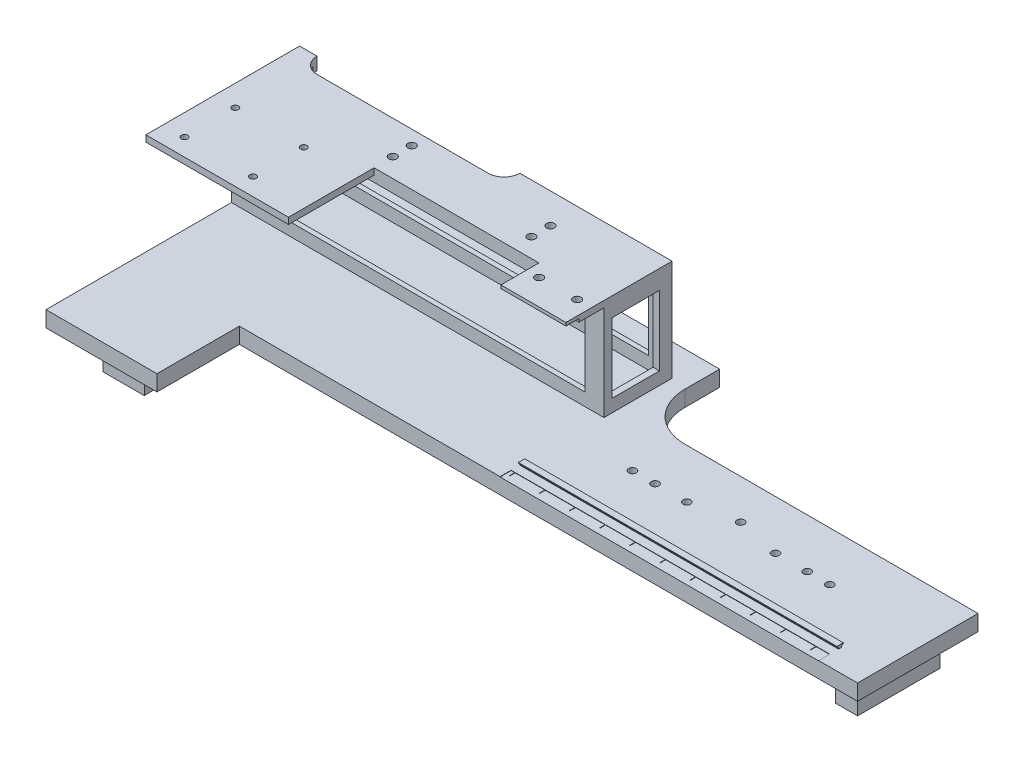
SolidWorks part; units mm, degrees
ref_plane "前视基准面" through (0, 0, 0) normal (0, 0, 1) x (1, 0, 0)
ref_plane "上视基准面" through (0, 0, 0) normal (0, 1, 0) x (1, 0, 0)
ref_plane "右视基准面" through (0, 0, 0) normal (1, 0, 0) x (0, 0, -1)
other "Configuration Table"
sketch "草图1" plane through (0, 0, 0) normal (0, 1, 0) x (1, 0, 0)
  line L1 (-1150, 300) -> (1150, 300)
  line L2 (-1150, 300) -> (-1150, -300)
  line L3 (-1150, -300) -> (1150, -300)
  line L4 (1150, 300) -> (1150, -300)
  line L5 (-1150, 300) -> (1150, -300) construction
  line L6 (-1150, -300) -> (1150, 300) construction
  point P0 (0, 0)
  dimension "D1" = 600
  dimension "D2" = 2300
extrude "凸台-拉伸1" add sketch "草图1" along normal blind 50
sketch "草图3" plane through (0, 0, 0) normal (0, -1, 0) x (1, 0, 0)
  line L1 (-1150, 300) -> (-800, 300)
  line L2 (-1150, 300) -> (-1150, 320)
  line L3 (-1150, 320) -> (-800, 320)
  line L4 (-800, 300) -> (-800, 320)
  dimension "D1" = 20
  dimension "D2" = 350
extrude "凸台-拉伸3" add sketch "草图3" against normal blind 50
sketch "草图5" plane through (0, 50, 0) normal (0, 1, 0) x (1, 0, 0)
  line L0 (-1150, 300) -> (-1150, -320) construction
  line L1 (-1150, -320) -> (-800, -320)
  line L2 (-1150, -320) -> (-1150, -800)
  line L3 (-1150, -800) -> (-800, -800)
  line L4 (-800, -320) -> (-800, -800)
  line L5 (-800, -300) -> (1150, -300) construction
  dimension "D1" = 350
  dimension "D2" = 500
extrude "凸台-拉伸4" add sketch "草图5" against normal blind 50
sketch "草图6" plane through (0, 50, 0) normal (0, 1, 0) x (1, 0, 0)
  line L0 (-1150, 300) -> (-1150, -800) construction
  line L1 (-1150, -580) -> (-800, -580)
  line L2 (-1150, -580) -> (-1150, -600)
  line L3 (-1150, -600) -> (-800, -600)
  line L4 (-800, -580) -> (-800, -600)
  line L5 (-800, -300) -> (-800, -800) construction
  line L6 (-800, -300) -> (1150, -300) construction
  line L7 (-1150, -800) -> (-800, -800) construction
  dimension "D1" = 280
  dimension "D2" = 200
extrude "凸台-拉伸5" add sketch "草图6" along normal blind 300
sketch "草图7" plane through (0, 0, 600) normal (0, 0, 1) x (1, 0, 0)
  line L0 (-1150, 350) -> (-800, 350) construction
  line L1 (-1150, 350) -> (-1150, 50) construction
  circle A0 centre (-1130, 330) radius 10
  circle A1 centre (-1095, 330) radius 10
  circle A2 centre (-1060, 330) radius 10
  circle A3 centre (-1025, 330) radius 10
  circle A4 centre (-990, 330) radius 10
  circle A5 centre (-955, 330) radius 10
  circle A6 centre (-920, 330) radius 10
  circle A7 centre (-885, 330) radius 10
  circle A8 centre (-850, 330) radius 10
  circle A9 centre (-815, 330) radius 10
  dimension "D1" = 20
  dimension "D2" = 20
  dimension "D3" = 20
  dimension "D4" = 10
extrude "切除-拉伸2" cut sketch "草图7" against normal blind 300
sketch "草图8" plane through (0, 0, 600) normal (0, 0, 1) x (1, 0, 0)
  line L1 (-1150, 350) -> (-1150, 50) construction
  circle A0 centre (-1112.5, 300) radius 10
  circle A1 centre (-1095, 330) radius 10 construction
  circle A2 centre (-1077.5, 300) radius 10
  circle A3 centre (-1042.5, 300) radius 10
  circle A4 centre (-1007.5, 300) radius 10
  circle A5 centre (-972.5, 300) radius 10
  circle A6 centre (-937.5, 300) radius 10
  circle A7 centre (-902.5, 300) radius 10
  circle A8 centre (-867.5, 300) radius 10
  circle A9 centre (-832.5, 300) radius 10
  dimension "D1" = 30
  dimension "D2" = 20
  dimension "D3" = 37.5
  dimension "D4" = 9
extrude "切除-拉伸3" cut sketch "草图8" against normal blind 50
pattern_linear "阵列(线性)1" count 4 spacing 60 along (0, -1, 0) of "切除-拉伸2", "切除-拉伸3"
chamfer "倒角1" distance 20 angle 45 1 edges at (-975, 50, 580)
chamfer "倒角2" distance 20 angle 45 1 edges at (-975, 50, 600)
sketch "草图11" plane through (0, 50, 0) normal (0, 1, 0) x (1, 0, 0)
  line L1 (-1020, -637.5367) -> (-930, -637.5367)
  line L2 (-1020, -637.5367) -> (-1020, -677.5367)
  line L3 (-1020, -677.5367) -> (-930, -677.5367)
  line L4 (-930, -637.5367) -> (-930, -677.5367)
extrude "切除-拉伸5" cut sketch "草图11" against normal blind 2
sketch "草图13" plane through (0, 50, 0) normal (0, 1, 0) x (1, 0, 0)
  line L0 (1135, -300) -> (1150, -300)
  line L1 (-800, -300) -> (-785, -300)
  line L2 (-800, -300) -> (-800, 300)
  line L3 (-800, 300) -> (1150, 300)
  line L4 (1150, -300) -> (1150, 300)
  line L6 (-785, -300) -> (-785, 285)
  line L7 (-785, 285) -> (1135, 285)
  line L8 (1135, -300) -> (1135, 285)
  dimension "D1" = 15
  dimension "D2" = 15
  dimension "D3" = 15
extrude "凸台-拉伸6" add sketch "草图13" along normal blind 400
sketch "草图14" plane through (-800, 0, 0) normal (-1, 0, 0) x (0, 0, 1)
  line L0 (300, 450) -> (300, 50) construction
  line L1 (-300, 450) -> (300, 450)
  line L2 (-300, 450) -> (-300, 350)
  line L3 (-300, 350) -> (300, 350)
  line L4 (300, 450) -> (300, 350)
  line L5 (-300, 50) -> (560, 50) construction
  dimension "D1" = 300
extrude "切除-拉伸7" cut sketch "草图14" against normal blind 2368
sketch "草图15" plane through (0, 50, 0) normal (0, 1, 0) x (1, 0, 0)
  line L0 (-1150, 300) -> (-1150, -560) construction
  line L1 (-1150, 100) -> (1209.5756, 100)
  line L2 (-1150, 100) -> (-1150, -299.8306)
  line L3 (-1150, -299.8306) -> (1209.5756, -299.8306)
  line L4 (1209.5756, 100) -> (1209.5756, -299.8306)
  dimension "D1" = 100
extrude "切除-拉伸8" cut sketch "草图15" along normal blind 2368
sketch "草图16" plane through (0, 50, 0) normal (0, 1, 0) x (1, 0, 0)
  line L0 (1150, -299.8306) -> (1150, 100) construction
  line L1 (-800, 100) -> (1150, 100)
  line L2 (-800, 100) -> (-800, 85)
  line L3 (-800, 85) -> (1150, 85)
  line L4 (1150, 100) -> (1150, 85)
  dimension "D1" = 15
extrude "凸台-拉伸7" add sketch "草图16" along normal up to surface (300 mm away) up to face at (175, 350, -196.25)
sketch "草图17" plane through (0, 350, 0) normal (0, 1, 0) x (1, 0, 0)
  line L1 (-1150, 300) -> (-800, 300)
  line L2 (-1150, 300) -> (-1150, -299.8306)
  line L3 (-1150, -299.8306) -> (-800, -299.8306)
  line L4 (-800, 85) -> (-800, -299.8306)
  line L5 (-800, 300) -> (1150, 300)
  line L7 (-800, 85) -> (1150, 85)
  line L8 (1150, 300) -> (1150, 85)
sketch "草图18" plane through (0, 50, 0) normal (0, 1, 0) x (1, 0, 0)
  circle A0 centre (-800, -300) radius 17.9938
extrude "切除-拉伸9" cut sketch "草图18" along normal blind 2368
extrude "凸台-拉伸11" add sketch "草图17" along normal blind 20
sketch "草图20" plane through (0, 50, 0) normal (0, 1, 0) x (1, 0, 0)
  circle A0 centre (1150, -300) radius 52.3169
extrude "切除-拉伸10" cut sketch "草图20" along normal blind 556
sketch "草图21" plane through (0, 0, -85) normal (0, 0, 1) x (1, 0, 0)
  line L0 (1110, 90) -> (1110, 330)
  line L1 (1110, 330) -> (-760, 330)
  line L2 (-760, 330) -> (-760, 330)
  line L3 (-760, 330) -> (-760, 90)
  line L4 (-760, 90) -> (1110, 90)
  line L5 (1150, 50) -> (1150, 370)
  line L6 (1150, 370) -> (-800, 370)
  line L7 (-800, 370) -> (-800, 350)
  line L8 (-800, 350) -> (-800, 50)
  line L9 (-800, 50) -> (1150, 50)
  line L10 (1150, 50) -> (1150, 370) construction
  line L11 (1150, 370) -> (-800, 370) construction
  line L12 (-800, 370) -> (-800, 350) construction
  line L13 (-800, 350) -> (-800, 50) construction
  line L14 (-800, 50) -> (1150, 50) construction
  dimension "D1" = 0
  dimension "D2" = 40
extrude "切除-拉伸11" cut sketch "草图21" against normal blind 556
sketch "草图22" plane through (-800, 0, 0) normal (-1, 0, 0) x (0, 0, 1)
  line L0 (-260, 90) -> (-125, 90)
  line L1 (-125, 90) -> (-125, 310)
  line L2 (-125, 310) -> (-260, 310)
  line L3 (-260, 310) -> (-260, 90)
  line L4 (-300, 50) -> (-85, 50)
  line L5 (-85, 50) -> (-85, 350)
  line L6 (-85, 350) -> (-300, 350)
  line L7 (-300, 350) -> (-300, 50)
  line L8 (-300, 50) -> (-85, 50) construction
  line L9 (-85, 50) -> (-85, 350) construction
  line L10 (-85, 350) -> (-300, 350) construction
  line L11 (-300, 350) -> (-300, 50) construction
  dimension "D1" = 0
  dimension "D2" = 40
extrude "切除-拉伸13" cut sketch "草图22" against normal blind 1998
sketch "草图23" plane through (-800, 0, 0) normal (-1, 0, 0) x (0, 0, 1)
  line L1 (-300, 350) -> (-85, 350)
  line L2 (-300, 350) -> (-300, 50)
  line L3 (-300, 50) -> (-85, 50)
  line L4 (-85, 350) -> (-85, 50)
extrude "切除-拉伸14" cut sketch "草图23" against normal blind 50
sketch "草图24" plane through (-750, 0, 0) normal (-1, 0, 0) x (0, 0, 1)
  line L1 (-300, 350) -> (-285, 350)
  line L2 (-300, 350) -> (-300, 330)
  line L3 (-300, 330) -> (-285, 330)
  line L4 (-285, 350) -> (-285, 330)
  line L5 (-100, 350) -> (-85, 350)
  line L6 (-100, 350) -> (-100, 330)
  line L7 (-100, 330) -> (-85, 330)
  line L8 (-85, 350) -> (-85, 330)
  line L9 (-300, 90) -> (-285, 90)
  line L10 (-300, 90) -> (-300, 50)
  line L11 (-300, 50) -> (-285, 50)
  line L12 (-285, 90) -> (-285, 50)
  line L13 (-100, 90) -> (-85, 90)
  line L14 (-100, 90) -> (-100, 50)
  line L15 (-100, 50) -> (-85, 50)
  line L16 (-85, 90) -> (-85, 50)
extrude "凸台-拉伸13" add sketch "草图24" along normal up to surface (400 mm away) up to face at (-1150, 104, 454)
sketch "草图25" plane through (-1150, 0, 0) normal (-1, 0, 0) x (0, 0, 1)
  line L1 (-85, 370) -> (-300, 370)
  line L2 (-85, 370) -> (-85, 0)
  line L3 (-85, 0) -> (-300, 0)
  line L4 (-300, 370) -> (-300, 0)
  line L5 (-125, 310) -> (-260, 310)
  line L6 (-125, 310) -> (-125, 90)
  line L7 (-125, 90) -> (-260, 90)
  line L8 (-260, 310) -> (-260, 90)
extrude "凸台-拉伸14" add sketch "草图25" against normal blind 30
sketch "草图26" plane through (0, 0, -85) normal (0, 0, 1) x (1, 0, 0)
  line L0 (1110, 90) -> (25, 90)
  line L2 (1110, 330) -> (-1120, 330) construction
  line L3 (-800, 370) -> (1150, 370) construction
  line L5 (25, 330) -> (25, 90)
  line L7 (-35, 330) -> (-35, 90)
  line L9 (-35, 330) -> (-35, 370)
  line L11 (25, 330) -> (25, 370)
  line L12 (-800, 0) -> (1150, 0) construction
  line L14 (-35, 90) -> (-35, 0)
  line L16 (25, 90) -> (25, 0)
  line L17 (-35, 90) -> (-1120, 90)
  line L18 (-35, 0) -> (25, 0)
  line L19 (-35, 370) -> (25, 370)
  line L20 (-35, 370) -> (25, 370)
  line L21 (-35, 370) -> (-35, 0)
  line L22 (-35, 0) -> (25, 0)
  line L23 (25, 370) -> (25, 0)
  line M10 (-1120, 330) -> (1110, 330)
  line M12 (1110, 90) -> (-1120, 90)
  line M16 (-1150, 50) -> (1150, 50)
  line M18 (1150, 370) -> (-800, 370)
extrude "凸台-拉伸16" add sketch "草图26" against normal up to surface (215 mm away) contours L7 L5 M10 M12 | L11 L9 M10 M18 | L16 L14 M12 M16 | L21 L20 L23 L22 region at (-5, 350, -85) region at (-5, 210, -85) region at (-5, 70, -85) up to face at (-5, 210, -300)
sketch "草图28" plane through (-35, 0, 0) normal (-1, 0, 0) x (0, 0, 1)
  line L1 (-285, 350) -> (-100, 350)
  line L2 (-285, 350) -> (-285, 50)
  line L3 (-285, 50) -> (-100, 50)
  line L4 (-100, 350) -> (-100, 50)
extrude "切除-拉伸16" cut sketch "草图28" against normal blind 89
sketch "草图29" plane through (0, 0, 0) normal (0, -1, 0) x (-1, 0, 0)
  line L1 (1150, 300) -> (-1150, 300)
  line L2 (1150, 300) -> (1150, 400)
  line L3 (1150, 400) -> (-1150, 400)
  line L4 (-1150, 300) -> (-1150, 400)
  dimension "D1" = 100
extrude "凸台-拉伸17" add sketch "草图29" against normal blind 50
sketch "草图30" plane through (0, 370, 0) normal (0, 1, 0) x (1, 0, 0)
  circle A0 centre (-1082.9308, 30) radius 10
  circle A1 centre (-1082.9308, -130) radius 10
  circle A2 centre (-867.0692, 30) radius 10
  circle A3 centre (-867.0692, -130) radius 10
extrude "切除-拉伸17" cut sketch "草图30" against normal blind 50
sketch "草图31" plane through (-800, 0, 0) normal (1, 0, 0) x (0, 0, -1)
  line L0 (-170, 370) -> (-170, 390) construction
  line L1 (-321.6973, 391.2845) -> (-185, 391.2845)
  line L2 (-321.6973, 391.2845) -> (-321.6973, 329.5415)
  line L3 (-321.6973, 329.5415) -> (-185, 329.5415)
  line L4 (-185, 391.2845) -> (-185, 329.5415)
  dimension "D1" = 15
extrude "切除-拉伸18" cut sketch "草图31" against normal through all both and the other way through all
sketch "草图32" plane through (0, 50, 0) normal (0, 1, 0) x (1, 0, 0)
  line L0 (1150, 85) -> (1150, -300) construction
  line L2 (1150, -107.5) -> (-729.851, -107.5) construction
  line L3 (-550, -107.5) -> (950, -107.5) construction
  line L4 (-550, -7.5) -> (950, -7.5)
  line L5 (-550, -207.5) -> (950, -207.5)
  arc A0 (-550, -7.5) -> (-550, -207.5) centre (-550, -107.5) ccw
  arc A1 (950, -207.5) -> (950, -7.5) centre (950, -107.5) ccw
  point P8 (200, -107.5)
  dimension "D2" = 1500
  dimension "D1" = 100
  dimension "D3" = 200
sketch "草图33" plane through (0, 50, 0) normal (0, 1, 0) x (1, 0, 0)
  line L0 (-1150, 400) -> (-1150, 750)
  line L1 (-1150, 750) -> (-800, 750)
  line L2 (-800, 400) -> (-800, 750)
  line L3 (-1150, 400) -> (1150, 400) construction
  line L4 (-1150, 400) -> (-800, 400)
  dimension "D1" = 350
extrude "凸台-拉伸18" add sketch "草图33" against normal up to surface (50 mm away) up to face at (-266.6667, 0, 233.3333)
sketch "草图34" plane through (0, 50, 0) normal (0, 1, 0) x (1, 0, 0)
  line L1 (-800, -300) -> (-1418.7431, -300)
  line L3 (-800, -918.0987) -> (-1418.7431, -918.0987)
  line L4 (-1418.7431, -300) -> (-1418.7431, -918.0987)
  line L5 (-800, -300) -> (-665.2437, -300)
  line L7 (-800, -918.0987) -> (-665.2437, -918.0987)
  line L8 (-665.2437, -300) -> (-665.2437, -918.0987)
extrude "切除-拉伸20" cut sketch "草图34" against normal through all both and the other way through all
sketch "草图35" plane through (0, 50, 0) normal (0, 1, 0) x (1, 0, 0)
  line L1 (-1150, -300) -> (-800, -300)
  line L2 (-1150, -300) -> (-1150, -500)
  line L3 (-1150, -500) -> (-800, -500)
  line L4 (-800, -300) -> (-800, -500)
  dimension "D1" = 200
extrude "凸台-拉伸19" add sketch "草图35" against normal up to surface (50 mm away) up to face at (-266.6667, 0, -283.3333)
sketch "草图36" plane through (0, 50, 0) normal (0, 1, 0) x (1, 0, 0)
  line L6 (-1150, 85) -> (-1150, -500) construction
  line L7 (-1150, -205) -> (-800, -205)
  line L8 (-1150, -205) -> (-1150, -220)
  line L9 (-1150, -220) -> (-800, -220)
  line L10 (-800, -205) -> (-800, -220)
  line L11 (-800, -185) -> (-1150, -185) construction
  line L12 (-800, -500) -> (-800, -300) construction
  dimension "D1" = 20
  dimension "D2" = 15
  dimension "D3" = 0
extrude "凸台-拉伸20" add sketch "草图36" along normal blind 200
sketch "草图37" plane through (0, 0, 220) normal (0, 0, 1) x (1, 0, 0)
  line L0 (-1150, 250) -> (-800, 250) construction
  line L1 (-1150, 250) -> (-1150, 50) construction
  circle A0 centre (-1130, 230) radius 10
  circle A1 centre (-1095, 230) radius 10
  circle A2 centre (-1060, 230) radius 10
  circle A3 centre (-1025, 230) radius 10
  circle A4 centre (-990, 230) radius 10
  circle A5 centre (-955, 230) radius 10
  circle A6 centre (-920, 230) radius 10
  circle A7 centre (-885, 230) radius 10
  circle A8 centre (-850, 230) radius 10
  circle A9 centre (-815, 230) radius 10
  dimension "D1" = 20
  dimension "D2" = 20
  dimension "D3" = 20
  dimension "D4" = 10
extrude "切除-拉伸21" cut sketch "草图37" against normal blind 200 and the other way through all
sketch "草图38" plane through (0, 0, 220) normal (0, 0, 1) x (1, 0, 0)
  line L0 (-1130, 230) -> (-1095, 230) construction
  line L1 (-1095, 230) -> (-1095, 200) construction
  line L2 (-1095, 200) -> (-1130, 200) construction
  line L3 (-1130, 200) -> (-1130, 230) construction
  circle A0 centre (-1112.5, 200) radius 10
  circle A2 centre (-1077.5, 200) radius 10
  circle A3 centre (-1042.5, 200) radius 10
  circle A4 centre (-1007.5, 200) radius 10
  circle A5 centre (-972.5, 200) radius 10
  circle A6 centre (-937.5, 200) radius 10
  circle A7 centre (-902.5, 200) radius 10
  circle A8 centre (-867.5, 200) radius 10
  circle A9 centre (-832.5, 200) radius 10
  dimension "D2" = 20
  dimension "D3" = 9
  dimension "D1" = 30
extrude "切除-拉伸22" cut sketch "草图38" against normal blind 200
pattern_linear "阵列(线性)2" count 3 spacing 60 along (0, -1, 0) of "切除-拉伸22", "切除-拉伸21"
chamfer "倒角3" distance 10 angle 45 2 edges at (-975, 50, 205) (-975, 50, 220)
sketch "草图39" plane through (0, 50, 0) normal (0, 1, 0) x (1, 0, 0)
  line L0 (-800, -230) -> (-1150, -230) construction
  line L1 (-800, -500) -> (1294.0617, -500)
  line L2 (-800, -500) -> (-800, -240)
  line L3 (-800, -240) -> (1294.0617, -240)
  line L4 (1294.0617, -500) -> (1294.0617, -240)
  dimension "D1" = 10
extrude "切除-拉伸23" cut sketch "草图39" against normal blind 200
sketch "草图40" plane through (0, 370, 0) normal (0, 1, 0) x (1, 0, 0)
  line L1 (-800, 85) -> (-700, 85)
  line L2 (-800, 85) -> (-800, -185)
  line L3 (-800, -185) -> (-700, -185)
  line L4 (-700, 85) -> (-700, -185)
  dimension "D1" = 100
extrude "凸台-拉伸21" add sketch "草图40" against normal up to surface (20 mm away) up to face at (-1082.9308, 350, 140)
sketch "草图41" plane through (0, 50, 0) normal (0, 1, 0) x (1, 0, 0)
  line L0 (-800, 400) -> (-800, 750) construction
  line L1 (-1150, 750) -> (-800, 750)
  line L2 (-1150, 750) -> (-1150, 565)
  line L3 (-1150, 565) -> (-800, 565)
  line L4 (-800, 750) -> (-800, 565)
  dimension "D1" = 185
extrude "切除-拉伸24" cut sketch "草图41" against normal blind 200
sketch "草图42" plane through (0, 370, 0) normal (0, 1, 0) x (1, 0, 0)
  line L0 (-1045, 300) -> (-505.14, 300) construction
  line L1 (1150, 300) -> (-1150, 300) construction
  line L2 (-1045, 350) -> (-505.14, 350)
  line L3 (-1045, 250) -> (-505.14, 250)
  line L4 (-1035, 328) -> (-1035, 318.2276) construction
  line L5 (-515.14, 320) -> (-515.14, 328) construction
  arc A0 (-1045, 350) -> (-1045, 250) centre (-1045, 300) ccw
  arc A1 (-505.14, 250) -> (-505.14, 350) centre (-505.14, 300) ccw
  point P4 (-775.07, 300)
  dimension "D1" = 10
  dimension "D2" = 10
  dimension "D3" = 50
extrude "切除-拉伸25" cut sketch "草图42" against normal blind 200
sketch "草图43" plane through (0, 0, -300) normal (0, 0, -1) x (-1, 0, 0)
  line L0 (800, 50) -> (-1150, 50) construction
  line L1 (-1476.0177, 591.952) -> (-25, 591.952)
  line L2 (-1476.0177, 591.952) -> (-1476.0177, 50)
  line L3 (-1476.0177, 50) -> (-25, 50)
  line L4 (-25, 591.952) -> (-25, 50)
extrude "切除-拉伸26" cut sketch "草图43" against normal blind 532
sketch "草图44" plane through (25, 0, 0) normal (1, 0, 0) x (0, 0, -1)
  line L1 (85, 370) -> (300, 370)
  line L2 (85, 370) -> (85, 50)
  line L3 (85, 50) -> (300, 50)
  line L4 (300, 370) -> (300, 50)
  line L5 (125, 310) -> (260, 310)
  line L6 (125, 310) -> (125, 90)
  line L7 (125, 90) -> (260, 90)
  line L8 (260, 310) -> (260, 90)
extrude "凸台-拉伸22" add sketch "草图44" against normal blind 20
sketch "草图45" plane through (0, 50, 0) normal (0, 1, 0) x (1, 0, 0)
  circle A0 centre (-1090.5229, 522) radius 12
  circle A1 centre (-1090.5229, 444) radius 12
  circle A2 centre (-859.4771, 522) radius 12
  circle A3 centre (-859.4771, 444) radius 12
extrude "切除-拉伸27" cut sketch "草图45" against normal blind 80
sketch "草图46" plane through (0, 370, 0) normal (0, 1, 0) x (1, 0, 0)
  circle A0 centre (-701.1779, 205) radius 12.5
  circle A1 centre (-701.1779, 145) radius 12.5
  circle A2 centre (-263.624, 205) radius 12.5
  circle A3 centre (-263.624, 145) radius 12.5
extrude "切除-拉伸28" cut sketch "草图46" against normal blind 70
sketch "草图47" plane through (25, 0, 0) normal (1, 0, 0) x (0, 0, -1)
  line L0 (5.9634, 540) -> (5.9634, 390) construction
  line L1 (85, 370) -> (5.9634, 370)
  line L2 (85, 370) -> (85, 350)
  line L3 (85, 350) -> (5.9634, 350)
  line L4 (5.9634, 360) -> (5.9634, 350)
  line L5 (-185, 370) -> (85, 370) construction
  line L7 (5.9634, 350) -> (5.9634, 360)
  line L8 (5.9634, 370) -> (-35, 370)
  line L9 (-35, 360) -> (-35, 370)
  line L10 (-35, 370) -> (85, 370)
  line L13 (-35, 360) -> (5.9634, 360)
  line L14 (5.9634, 350) -> (5.9634, 360)
  line L15 (5.9634, 350) -> (85, 350)
  line L16 (85, 370) -> (-35, 370)
  line L17 (-35, 360) -> (5.9634, 360)
  line M12 (85, 370) -> (85, 50)
  dimension "D1" = 20
  dimension "D2" = 120
extrude "凸台-拉伸23" add sketch "草图47" against normal up to surface (205 mm away) contours L9 L13 L4 L3 L1 L8 M12 region at (25, 361.029, -33.1332)
sketch "草图48" plane through (0, 370, 0) normal (0, 1, 0) x (1, 0, 0)
  circle A0 centre (-140, 45.4817) radius 12.5
  circle A1 centre (-20, 45.4817) radius 12.5
extrude "切除-拉伸29" cut sketch "草图48" against normal blind 30
sketch "草图50" plane through (0, 50, 0) normal (0, 1, 0) x (1, 0, 0)
  line L0 (25, 300) -> (25, 463.9214)
sketch "草图51" plane through (0, 50, 0) normal (0, 1, 0) x (1, 0, 0)
  line L0 (1150, 140) -> (225, 140)
  line L1 (1150, 400) -> (1150, -240) construction
  line L2 (1150, -240) -> (-800, -240) construction
  line L5 (-800, 400) -> (1150, 400) construction
  line L6 (75, 400) -> (1150, 400)
  line L7 (1150, 400) -> (1150, 140)
  line L8 (75, 400) -> (75, 290)
  arc A0 (75, 290) -> (225, 140) centre (225, 290) ccw
  dimension "D2" = 150
  dimension "D1" = 380
  dimension "D3" = 1075
extrude "切除-拉伸31" cut sketch "草图51" against normal through all both and the other way through all
sketch "草图52" plane through (0, 50, 0) normal (0, 1, 0) x (1, 0, 0)
  line L0 (1150, -240) -> (-800, -240) construction
  line L1 (1030, -68.091) -> (1030, -28.091) construction
  line L2 (1030, -48.091) -> (1012.5, -48.091) construction
  line L4 (1027.5, 110) -> (1027.5, -90)
  line L7 (25, 300) -> (25, -35) construction
  line L8 (27.5, 110) -> (25, 110)
  line L9 (27.5, 110) -> (42.5, 110)
  line L10 (225, 140) -> (1150, 140) construction
  line L12 (42.5, -90) -> (1012.5, -90)
  line L14 (27.5, -105) -> (1027.5073, -105)
  line L15 (1027.5073, -105) -> (1027.5, -90)
  line L16 (1012.5, -90) -> (1012.5, 110)
  line L17 (42.5, -90) -> (42.5, 110)
  line L18 (1012.5, 110) -> (1027.5, 110)
  line L19 (42.5, -48.091) -> (25, -48.091) construction
  line L21 (27.5, -105) -> (25, -105)
  line L22 (25, 110) -> (25, -105)
  point P1 (527.5, -48.091)
  point P4 (527.5, -48.091)
  dimension "D1" = 150
  dimension "D2" = 30
  dimension "D3" = 15
  dimension "D4" = 15
extrude "凸台-拉伸24" add sketch "草图52" along normal blind 250 contours L14 L15 L4 L18 L16 L12 L17 L9 L8 L22 L21
sketch "草图53" plane through (25, 0, 0) normal (1, 0, 0) x (0, 0, -1)
  line L0 (150.071, 90) -> (110, 90)
  line L1 (125, 90) -> (260, 90) construction
  line L2 (110, 300) -> (110, 50) construction
  line L3 (110, 90) -> (110, 310)
  line L4 (110, 310) -> (177.1058, 310)
  line L5 (260, 310) -> (125, 310) construction
  line L6 (177.1058, 310) -> (150.071, 90)
extrude "切除-拉伸32" cut sketch "草图53" against normal mid plane 50
sketch "草图54" plane through (0, 0, -110) normal (0, 0, -1) x (-1, 0, 0)
  line L0 (-1012.5, 300) -> (-997.5, 260)
  line L1 (-997.5, 260) -> (-1012.5, 260)
  line L2 (-1012.5, 300) -> (-1012.5, 50) construction
  line L4 (-1012.5, 260) -> (-1012.5, 300)
extrude "凸台-拉伸25" add sketch "草图54" against normal up to surface (200 mm away) up to face at (527.5, 175, 90)
sketch "草图55" plane through (42.5, 0, 0) normal (1, 0, 0) x (0, 0, -1)
  line L0 (-90, 300) -> (-75, 260)
  line L1 (-75, 260) -> (-90, 260)
  line L2 (-90, 260) -> (-90, 300)
extrude "凸台-拉伸26" add sketch "草图55" along normal up to surface (985 mm away) up to face at (1027.5, 175, -10)
sketch "草图56" plane through (0, 0, -110) normal (0, 0, -1) x (-1, 0, 0)
  line L0 (-42.5, 300) -> (-57.5, 260)
  line L1 (-57.5, 260) -> (-42.5, 260)
  line L3 (-42.5, 300) -> (-42.5, 50) construction
  line L4 (-42.5, 260) -> (-42.5, 300)
extrude "凸台-拉伸27" add sketch "草图56" against normal up to surface (215 mm away) up to face at (526.2537, 175, 105)
sketch "草图57" plane through (25, 0, 0) normal (-1, 0, 0) x (0, 0, 1)
  line L0 (105, 180) -> (105, 170)
  line L1 (110, 180) -> (112.5, 185)
  line L2 (105, 180) -> (110, 180)
  line L4 (105, 170) -> (110, 170)
  line L8 (112.5, 185) -> (115, 185)
  line L9 (115, 185) -> (115, 165)
  line L10 (115, 165) -> (112.5, 165)
  line L11 (112.5, 165) -> (110, 170)
  point P4 (105, 175)
  dimension "D1" = 10
  dimension "D4" = 10
  dimension "D5" = 10
  dimension "D6" = 2.5
  dimension "D7" = 2.5
extrude "凸台-拉伸28" add sketch "草图57" against normal up to surface (1002.5 mm away) up to face at (1027.5, 175, -10)
sketch "草图58" plane through (0, 50, 0) normal (0, 1, 0) x (1, 0, 0)
  line L0 (1027.5073, -105) -> (1027.5073, -240) construction
  line L1 (1150, -240) -> (-800, -240) construction
  line L2 (1173.3497, -172.5) -> (-79.877, -172.5) construction
  line L4 (22.5073, -167.5) -> (1027.5073, -167.5)
  line L5 (22.5073, -167.5) -> (22.5073, -177.5)
  line L6 (22.5073, -177.5) -> (1027.5073, -177.5)
  line L7 (1027.5073, -167.5) -> (1027.5073, -177.5)
  dimension "D1" = 5
  dimension "D2" = 5
  dimension "D3" = 1005
extrude "凸台-拉伸29" add sketch "草图58" along normal blind 5
sketch "草图59" plane through (1027.5073, 0, 0) normal (1, 0, 0) x (0, 0, -1)
  line L0 (-177.5, 55) -> (-182.5, 57.5)
  line L1 (-182.5, 57.5) -> (-182.5, 60)
  line L2 (-182.5, 60) -> (-162.5, 60)
  line L3 (-162.5, 60) -> (-162.5, 57.5)
  line L4 (-162.5, 57.5) -> (-167.5, 55)
  line L5 (-172.5, 55) -> (-172.5, 40.0709) construction
  line L6 (-177.5, 55) -> (-167.5, 55) construction
  line L7 (-177.5, 55) -> (-167.5, 55)
  dimension "D1" = 2.5
  dimension "D2" = 2.5
  dimension "D3" = 5
  dimension "D4" = 10
  dimension "D5" = 10
extrude "凸台-拉伸30" add sketch "草图59" against normal up to surface (1005 mm away) up to face at (22.5073, 52.5, 172.5)
sketch "草图60" plane through (1027.5, 0, 0) normal (1, 0, 0) x (0, 0, -1)
  line L0 (-240, 50) -> (-200, 50)
  line L1 (140, 50) -> (-240, 50) construction
  line L2 (-200, 50) -> (-200, 90)
  line L3 (-200, 90) -> (-107.2068, 268.3128)
  line L4 (-107.2068, 268.3128) -> (-105, 268.3128)
  line L5 (-105, 300) -> (-105, 50) construction
  line L6 (-105, 268.3128) -> (-105, 50)
  line L7 (-105, 50) -> (-200, 50)
  dimension "D1" = 40
  dimension "D2" = 40
sketch "草图61" plane through (0, 50, 0) normal (0, 1, 0) x (1, 0, 0)
  line L0 (1150, -240) -> (-800, -240) construction
  line L1 (1027.5073, -240) -> (22.5073, -240)
  line L2 (1027.5073, -240) -> (1027.5073, -205)
  line L3 (1027.5073, -205) -> (22.5073, -205)
  line L4 (22.5073, -240) -> (22.5073, -205)
  dimension "D1" = 35
extrude "切除-拉伸33" cut sketch "草图61" against normal blind 1 and the other way through all
sketch "草图62" plane through (0, 49, 0) normal (0, 1, 0) x (1, 0, 0)
  line L0 (22.5073, -240) -> (1027.5073, -240) construction
  line L1 (34.939, -240) -> (33.939, -240)
  line L2 (34.939, -240) -> (34.939, -205)
  line L3 (34.939, -205) -> (33.939, -205)
  line L4 (33.939, -240) -> (33.939, -205)
  line L5 (22.5073, -205) -> (1027.5073, -205) construction
  line L6 (34.439, -240) -> (34.439, -205) construction
  line L8 (129.939, -240) -> (128.939, -240)
  line L9 (129.939, -240) -> (129.939, -205)
  line L10 (129.939, -205) -> (128.939, -205)
  line L11 (128.939, -240) -> (128.939, -205)
  line L12 (129.439, -240) -> (129.439, -205) construction
  line L13 (224.939, -240) -> (223.939, -240)
  line L14 (224.939, -240) -> (224.939, -205)
  line L15 (224.939, -205) -> (223.939, -205)
  line L16 (223.939, -240) -> (223.939, -205)
  line L17 (224.439, -240) -> (224.439, -205) construction
  line L18 (319.939, -240) -> (318.939, -240)
  line L19 (319.939, -240) -> (319.939, -205)
  line L20 (319.939, -205) -> (318.939, -205)
  line L21 (318.939, -240) -> (318.939, -205)
  line L22 (319.439, -240) -> (319.439, -205) construction
  line L23 (414.939, -240) -> (413.939, -240)
  line L24 (414.939, -240) -> (414.939, -205)
  line L25 (414.939, -205) -> (413.939, -205)
  line L26 (413.939, -240) -> (413.939, -205)
  line L27 (414.439, -240) -> (414.439, -205) construction
  line L28 (509.939, -240) -> (508.939, -240)
  line L29 (509.939, -240) -> (509.939, -205)
  line L30 (509.939, -205) -> (508.939, -205)
  line L31 (508.939, -240) -> (508.939, -205)
  line L32 (509.439, -240) -> (509.439, -205) construction
  line L33 (604.939, -240) -> (603.939, -240)
  line L34 (604.939, -240) -> (604.939, -205)
  line L35 (604.939, -205) -> (603.939, -205)
  line L36 (603.939, -240) -> (603.939, -205)
  line L37 (604.439, -240) -> (604.439, -205) construction
  line L38 (699.939, -240) -> (698.939, -240)
  line L39 (699.939, -240) -> (699.939, -205)
  line L40 (699.939, -205) -> (698.939, -205)
  line L41 (698.939, -240) -> (698.939, -205)
  line L42 (699.439, -240) -> (699.439, -205) construction
  line L43 (794.939, -240) -> (793.939, -240)
  line L44 (794.939, -240) -> (794.939, -205)
  line L45 (794.939, -205) -> (793.939, -205)
  line L46 (793.939, -240) -> (793.939, -205)
  line L47 (794.439, -240) -> (794.439, -205) construction
  line L48 (889.939, -240) -> (888.939, -240)
  line L49 (889.939, -240) -> (889.939, -205)
  line L50 (889.939, -205) -> (888.939, -205)
  line L51 (888.939, -240) -> (888.939, -205)
  line L52 (889.439, -240) -> (889.439, -205) construction
  line L53 (984.939, -240) -> (983.939, -240)
  line L54 (984.939, -240) -> (984.939, -205)
  line L55 (984.939, -205) -> (983.939, -205)
  line L56 (983.939, -240) -> (983.939, -205)
  line L57 (984.439, -240) -> (984.439, -205) construction
  dimension "D1" = 11
  dimension "D2" = 0.5
extrude "凸台-拉伸31" add sketch "草图62" along normal blind 1
sketch "草图63" plane through (0, 49, 0) normal (0, 1, 0) x (1, 0, 0)
  line L0 (1027.5073, -205) -> (1027.5073, -240) construction
  line L1 (22.5073, -240) -> (1027.5073, -240)
  line L2 (22.5073, -240) -> (22.5073, -222.5)
  line L3 (22.5073, -222.5) -> (1027.5073, -222.5)
  line L4 (1027.5073, -240) -> (1027.5073, -222.5)
extrude "切除-拉伸34" cut sketch "草图63" along normal blind 26
sketch "草图64" plane through (0, 49, 0) normal (0, 1, 0) x (1, 0, 0)
  line L0 (22.5073, -230) -> (1027.5073, -230)
  line L1 (22.5073, -240) -> (22.5073, -205) construction
  line L2 (1027.5073, -205) -> (1027.5073, -240) construction
  line L3 (22.5073, -240) -> (1027.5073, -240) construction
  text T0 "      0                                                  100                                                  200                                                 300                                                  400                                                 500                                                 600                                                 700                                                  800                                                 900                                                 1000"
  dimension "D1" = 10
sketch "草图65" plane through (0, 0, 0) normal (0, -1, 0) x (1, 0, 0)
  line L0 (-800, 240) -> (-800, 500) construction
  line L1 (-1040, 430) -> (-910, 430)
  line L2 (-1040, 430) -> (-1040, 360)
  line L3 (-1040, 360) -> (-910, 360)
  line L4 (-910, 430) -> (-910, 360)
  line L5 (-1040, -425) -> (-910, -425)
  line L6 (-1040, -425) -> (-1040, -495)
  line L7 (-1040, -495) -> (-910, -495)
  line L8 (-910, -425) -> (-910, -495)
  line L13 (1020, 180) -> (1090, 180)
  line L14 (1020, 180) -> (1020, -80)
  line L15 (1020, -80) -> (1090, -80)
  line L16 (1090, 180) -> (1090, -80)
  line L17 (-1150, -565) -> (-1150, 500) construction
  line L18 (-800, 500) -> (-1150, 500) construction
  line L19 (-1150, -565) -> (-800, -565) construction
  line L20 (-800, -565) -> (-800, -400) construction
  line L21 (-800, -400) -> (75, -400) construction
  line L22 (1150, 240) -> (-800, 240) construction
  line L23 (225, -140) -> (1150, -140) construction
  line L24 (1150, 240) -> (1150, -140) construction
  circle A0 centre (-650, 60) radius 50
  circle A1 centre (-650, -220) radius 50
  circle A2 centre (-250, -80) radius 50
  dimension "D1" = 100
  dimension "D10" = 500
  dimension "D11" = 180
  dimension "D12" = 180
  dimension "D13" = 400
  dimension "D14" = 320
  dimension "D2" = 500
  dimension "110" = 110
  dimension "D3" = 110
  dimension "D4" = 70
  dimension "D5" = 70
  dimension "D6" = 70
  dimension "D7" = 110
  dimension "D8" = 110
  dimension "D9" = 70
  dimension "D15" = 60
  dimension "D16" = 60
  dimension "D17" = 60
  dimension "D18" = 70
extrude "凸台-拉伸32" add sketch "草图65" along normal blind 100
sketch "草图66" plane through (0, 50, 0) normal (0, 1, 0) x (1, 0, 0)
  line L0 (-1136.9236, -190.6661) -> (-1176.256, -189.2469)
  line L1 (-1176.256, -189.2469) -> (-1170.5791, -239.3247)
  line L2 (-1170.5791, -239.3247) -> (-778.8001, -259.2983)
  line L3 (-778.8001, -259.2983) -> (-783.4246, -190.6661)
  line L4 (-783.4246, -190.6661) -> (-1136.9236, -190.6661)
extrude "切除-拉伸35" cut sketch "草图66" along normal blind 238
sketch "草图67" plane through (0, 50, 0) normal (0, 1, 0) x (1, 0, 0)
  line L0 (997.5, 110) -> (1012.5, 110)
  line L2 (57.5, 110) -> (57.5, -75)
  line L3 (57.5, -75) -> (997.5, -75)
  line L4 (997.5, 110) -> (997.5, -75)
  line L5 (42.5, 110) -> (57.5, 110)
  line L6 (42.5, 110) -> (42.5, -90)
  line L7 (42.5, -90) -> (1012.5, -90)
  line L8 (1012.5, 110) -> (1012.5, -90)
extrude "凸台-拉伸33" add sketch "草图67" along normal up to surface (210 mm away) up to face at (527.5, 260, -13.75)
sketch "草图68" plane through (1027.5, 0, 0) normal (1, 0, 0) x (0, 0, -1)
  line L10 (-2.5, 100) -> (-2.5, 106.3328)
  line L11 (7.5, 100) -> (7.5, 106.3328)
  line L12 (-7.1222, 122.3318) -> (-75, 230)
  line L13 (12.1222, 122.3318) -> (80, 230)
  line L14 (-75, 230) -> (-75, 50)
  line L15 (80, 230) -> (80, 50)
  line L16 (140, 50) -> (-240, 50) construction
  line L17 (80, 50) -> (-75, 50)
  line L18 (110, 300) -> (110, 50) construction
  arc A0 (-2.5, 100) -> (7.5, 100) centre (2.5, 100) ccw
  arc A1 (7.5, 106.3328) -> (12.1222, 122.3318) centre (37.5, 106.3328) cw
  arc A2 (-2.5, 106.3328) -> (-7.1222, 122.3318) centre (-32.5, 106.3328) ccw
  point P7 (7.5, 115)
  point P13 (-2.5, 115)
  dimension "D2" = 10
  dimension "D1" = 30
  dimension "D3" = 15
  dimension "D4" = 15
  dimension "D5" = 180
  dimension "D6" = 30
  dimension "D7" = 77.5
  dimension "D8" = 50
  dimension "D9" = 180
extrude "凸台-拉伸34" add sketch "草图68" against normal up to surface (970 mm away) up to face at (57.5, 155, -17.5)
sketch "草图69" plane through (57.5, 0, 0) normal (1, 0, 0) x (0, 0, -1)
  line L0 (110, 300) -> (110, 50)
  line L2 (80, 50) -> (80, 260)
  line L4 (110, 50) -> (80, 50)
  line L5 (-75, 260) -> (110, 260) construction
  line L6 (80, 260) -> (95, 300)
  line L7 (110, 300) -> (-90, 300) construction
  line L8 (95, 300) -> (110, 300)
  dimension "D1" = 15
extrude "凸台-拉伸35" add sketch "草图69" along normal up to surface (970 mm away) up to face at (1027.5, 175, -10)
extrude "凸台-拉伸36" add sketch "草图69<2>" against normal up to surface (32.5 mm away) up to face at (25, 175, 77.0833)
sketch "草图69<2>" plane through (57.5, 0, 0) normal (1, 0, 0) x (0, 0, -1) same geometry as "草图69"
fillet "圆角1" radius 30 2 edges at (527.5, 230, 75) (527.5, 230, -80)
sketch "草图70" plane through (1027.5, 0, 0) normal (1, 0, 0) x (0, 0, -1)
  circle A0 centre (2.5, 100) radius 5
extrude "切除-拉伸37" cut sketch "草图70" against normal through all both and the other way through all
chamfer "倒角4" distance 5 angle 45 1 edges at (1027.5, 100, -7.5)
chamfer "倒角5" distance 5 angle 45 1 edges at (25, 100, -7.5)
sketch "草图71" plane through (1027.5, 0, 0) normal (1, 0, 0) x (0, 0, -1)
  line L0 (-142.2905, 310.0271) -> (-149.6095, 50)
  line L1 (140, 50) -> (-240, 50) construction
  line L2 (-149.6095, 50) -> (140, 50)
  line L3 (140, 50) -> (140, 329.9785)
  line L4 (140, 329.9785) -> (-142.2905, 310.0271)
extrude "切除-拉伸39" cut sketch "草图71" against normal up to surface (1002.5 mm away) up to face at (25, 261.4286, -119.4233)
sketch "草图72" plane through (0, 50, 0) normal (0, 1, 0) x (1, 0, 0)
  circle A0 centre (1012.6782, -59.3485) radius 70.1156
extrude "切除-拉伸40" cut sketch "草图72" along normal blind 359
sketch "草图73" plane through (0, 50, 0) normal (0, 1, 0) x (1, 0, 0)
  line L0 (326.2573, -15) -> (175.0073, -15) construction
  line L1 (326.2573, 45) -> (326.2573, -75) construction
  line L2 (175.0073, -75) -> (175.0073, 45) construction
  line L3 (726.2573, -15) -> (877.5073, -15) construction
  line L4 (726.2573, -75) -> (726.2573, 45) construction
  line L5 (877.5073, 45) -> (877.5073, -75) construction
  circle A0 centre (215.0073, -15) radius 12
  circle A1 centre (286.2573, -15) radius 12
  circle A2 centre (766.2573, -15) radius 12
  circle A3 centre (837.5073, -15) radius 12
  dimension "D1" = 24
  dimension "D2" = 24
  dimension "D3" = 40
  dimension "D4" = 40
  dimension "D5" = 24
  dimension "D6" = 24
  dimension "D7" = 40
  dimension "D8" = 40
extrude "切除-拉伸41" cut sketch "草图73" against normal through all both and the other way through all
sketch "草图74" plane through (0, 50, 0) normal (0, 1, 0) x (1, 0, 0)
  circle A0 centre (526.2573, 15) radius 12
  circle A1 centre (666.2573, -15) radius 12
  circle A2 centre (386.2573, -15) radius 12
  point P9 (386.2573, -15)
  dimension "D1" = 24
extrude "切除-拉伸42" cut sketch "草图74" against normal through all both and the other way through all
sketch "草图75" plane through (0, 0, 0) normal (0, -1, 0) x (1, 0, 0)
  line L1 (-766.3381, 149.9068) -> (-94.0714, 149.9068)
  line L2 (-766.3381, 149.9068) -> (-766.3381, -357.1612)
  line L3 (-766.3381, -357.1612) -> (-94.0714, -357.1612)
  line L4 (-94.0714, 149.9068) -> (-94.0714, -357.1612)
